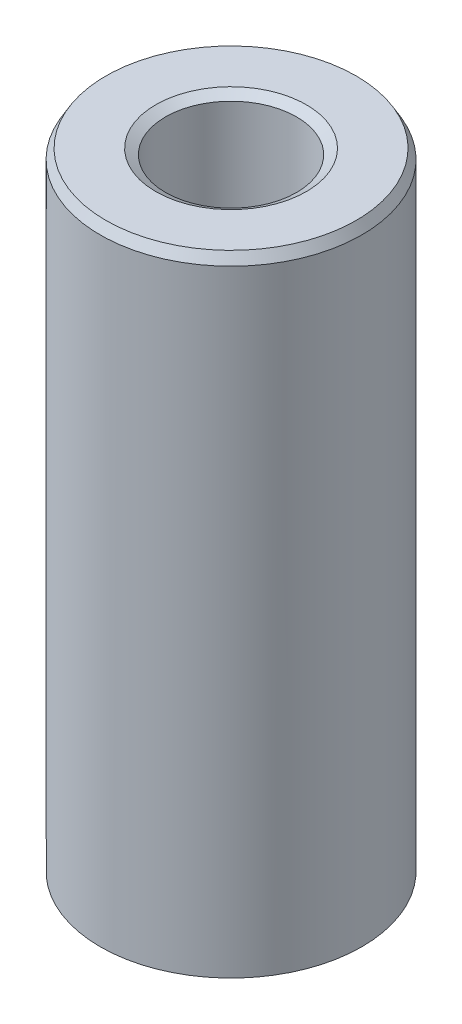
SolidWorks part; units mm, degrees
ref_plane "Front Plane" through (0, 0, 0) normal (0, 0, 1) x (1, 0, 0)
ref_plane "Top Plane" through (0, 0, 0) normal (0, 1, 0) x (1, 0, 0)
ref_plane "Right Plane" through (0, 0, 0) normal (1, 0, 0) x (0, 0, -1)
sketch "Sketch1" plane through (0, 0, 0) normal (0, 1, 0) x (1, 0, 0)
  circle A0 centre (0, 0) radius 47.5
  dimension "SLEEVE_OD" = 95
extrude "Boss-Extrude1" add sketch "Sketch1" along normal blind 229.4617
sketch "Sketch2" plane through (0, 0, 0) normal (0, 1, 0) x (1, 0, 0)
  circle A0 centre (0, 0) radius 23.7962
  dimension "BORE_D" = 47.5924
extrude "Cut-Extrude1" cut sketch "Sketch2" along normal through all
chamfer "Chamfer1" distance 3.5468 angle 30 4 edges at (0, 229.4617, 23.7962) (0, 0, 23.7962) (0, 0, 47.5) (0, 229.4617, 47.5) first distance on face at (0, 229.4617, 23.7962) first distance on face at (0, 0, 23.7962) first distance on face at (0, 229.4617, 47.5)
